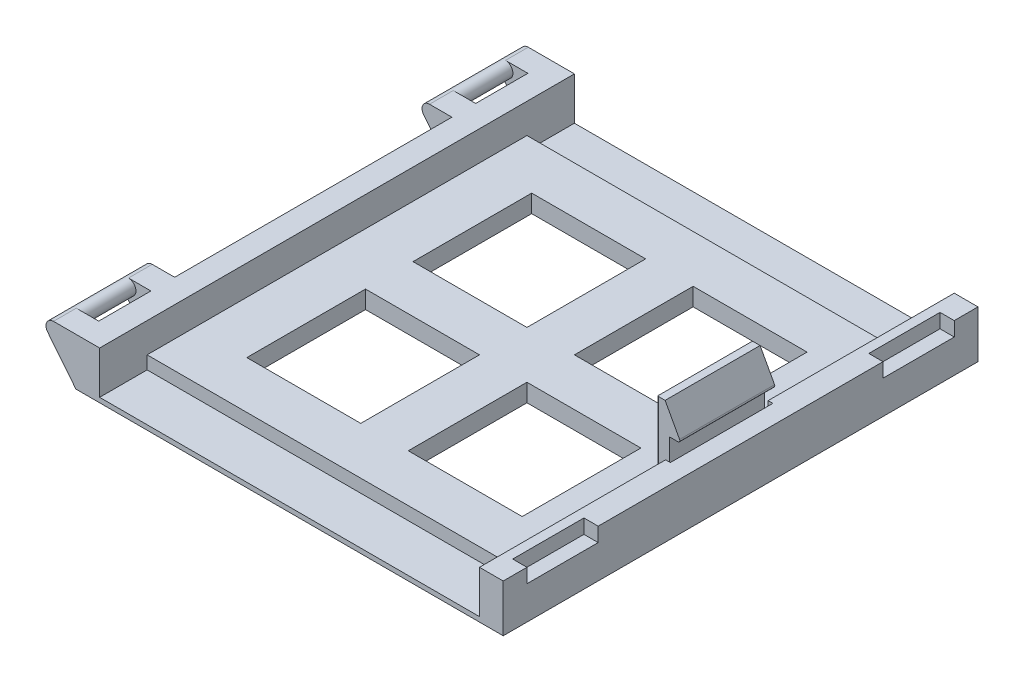
SolidWorks part; units mm, degrees
material "ABS"
ref_plane "Front Plane" through (0, 0, 0) normal (0, 0, 1) x (1, 0, 0)
ref_plane "Top Plane" through (0, 0, 0) normal (0, 1, 0) x (1, 0, 0)
ref_plane "Right Plane" through (0, 0, 0) normal (1, 0, 0) x (0, 0, -1)
sketch "Sketch1" plane through (0, 0, 0) normal (0, 0, 1) x (1, 0, 0)
  line L0 (23.8125, 6.35) -> (23.8125, 9.525)
  line L1 (-28.575, 3.175) -> (28.575, 3.175)
  line L2 (-28.575, 3.175) -> (-28.575, -3.175)
  line L3 (-28.575, -3.175) -> (28.575, -3.175)
  line L4 (28.575, 3.175) -> (28.575, -3.175)
  line L5 (-25.4, 3.175) -> (25.4, 3.175)
  line L6 (-25.4, 3.175) -> (-25.4, -0.7938)
  line L7 (-25.4, -0.7938) -> (25.4, -0.7938)
  line L8 (25.4, 3.175) -> (25.4, -0.7938)
  line L9 (-28.575, 3.175) -> (28.575, 3.175) construction
  line L10 (-28.575, 3.175) -> (-28.575, 9.525) construction
  line L11 (-28.575, 9.525) -> (28.575, 9.525) construction
  line L12 (28.575, 3.175) -> (28.575, 9.525) construction
  line L13 (-25.4, 3.175) -> (25.4, 3.175) construction
  line L14 (-25.4, 3.175) -> (-25.4, 7.1437) construction
  line L15 (-25.4, 7.1437) -> (25.4, 7.1437) construction
  line L16 (25.4, 3.175) -> (25.4, 7.1437) construction
  line L21 (25.4, -0.7938) -> (25.4, 5.588)
  line L22 (26.7661, 5.9634) -> (24.8285, 9.525)
  line L23 (24.8285, 9.525) -> (23.8125, 9.525)
  line L24 (-28.575, -3.175) -> (-32.3558, 1.5502)
  line L25 (-31.575, 3.175) -> (-28.575, 3.175)
  line L26 (-30.575, 2.175) -> (-28.575, 2.175) construction
  line L27 (25.4, -2.0638) -> (25.4, -0.7938)
  line L28 (23.8125, -0.7938) -> (23.8125, -2.0638)
  line L29 (23.1775, -2.0638) -> (23.1775, -0.7938)
  line L30 (23.8125, -0.7938) -> (23.8125, 6.35)
  line L33 (26.543, 5.588) -> (25.4, 5.588)
  line L34 (25.4, 5.588) -> (25.4, 3.175)
  line L35 (26.035, 3.175) -> (26.035, -2.0638)
  line L36 (26.797, 6.1869) -> (26.797, 5.0154) construction
  arc A0 (26.035, -2.0638) -> (25.4, -2.0638) centre (25.7175, -2.0638) cw
  arc A1 (23.8125, -2.0638) -> (23.1775, -2.0638) centre (23.495, -2.0638) cw
  arc A2 (-32.3558, 1.5502) -> (-31.575, 3.175) centre (-31.575, 2.175) cw
  circle A3 centre (-31.575, 2.175) radius 1
  arc A6 (26.7661, 5.9634) -> (26.543, 5.588) centre (26.543, 5.842) cw
  point P4 (0, -3.175)
  point P6 (-28.575, 0)
  point P16 (0, -0.7938)
  dimension "D10" = 1.27
  dimension "D13" = 1
  dimension "D21" = 0.254
  dimension "D6" = 0.3175
  dimension "D1" = 57.15
  dimension "D2" = 6.35
  dimension "D3" = 12.7
  dimension "D4" = 7.9375
  dimension "D5" = 50.8
  dimension "D7" = 1.016
  dimension "D8" = 1.5875
  dimension "D9" = 2.413
  dimension "D14" = 2
  dimension "D22" = 1.397
extrude "Boss-Extrude1" add sketch "Sketch1" along normal mid plane 63.5 contours L1 L8 L7 L6 L2 L3 | L28 L7 | L35 L1 L8 region at (-0.716, -1.5305, 0) region at (25.7175, 0.4305, 0) region at (23.495, -1.5551, 0)
extrude "Boss-Extrude2" add sketch "Sketch1<3>" along normal mid plane 12.7 contours L4 | A6 L30 L5 L34 L33 | L30 L7 L8 L5 | L0 region at (24.8321, 6.3195, 0) region at (24.6062, 1.1906, 0)
sketch "Sketch1<3>" plane through (0, 0, 0) normal (0, 0, 1) x (1, 0, 0) same geometry as "Sketch1"
extrude "Cut-Extrude2" cut sketch "Sketch1<6>" against normal mid plane 12.827 contours L35 L1 L8 region at (25.7175, 0.4305, 0)
sketch "Sketch1<6>" plane through (0, 0, 0) normal (0, 0, 1) x (1, 0, 0) same geometry as "Sketch1"
sketch "Sketch7" plane through (0, -0.7938, 0) normal (0, 1, 0) x (1, 0, 0)
  line L0 (26.035, 6.35) -> (23.9395, 6.35)
  line L3 (23.9395, -6.35) -> (26.035, -6.35)
  line L6 (23.8125, 6.223) -> (23.8125, -6.223)
  line L7 (23.8125, 6.35) -> (25.4, 6.35) construction
  line L10 (26.7661, -6.35) -> (24.8285, -6.35) construction
  line L11 (26.035, 6.4135) -> (26.035, -6.4135) construction
  line L12 (26.7661, 6.35) -> (24.8285, 6.35) construction
  line L13 (23.8125, -6.35) -> (23.8125, 6.35) construction
  arc A0 (23.9395, 6.35) -> (23.8125, 6.223) centre (23.9395, 6.223) ccw
  arc A1 (23.8125, -6.223) -> (23.9395, -6.35) centre (23.9395, -6.223) ccw
  dimension "D1" = 0.127
sketch "Sketch8" plane through (26.035, 0, 0) normal (1, 0, 0) x (0, 0, -1)
  line L4 (-6.858, -2.6988) -> (-6.858, 9.525)
  line L5 (-6.858, 9.525) -> (-6.35, 9.525)
  line L6 (-6.35, 9.525) -> (-6.35, -2.6988)
  arc A0 (-6.35, -2.6988) -> (-6.858, -2.6988) centre (-6.604, -2.6988) cw
  dimension "D1" = 0.254
  dimension "D2" = 1.905
sweep "Cut-Sweep1" cut profiles "Sketch8" path "Sketch7"
extrude "Boss-Extrude3" add sketch "Sketch1<7>" against normal blind 3.048 from surface contours A2 L24 L2 L25 | A2 A3 region at (-29.726, 0.631, 0) region at (-31.575, 2.175, 0) starting at face at (0, 0.5953, 31.75)
sketch "Sketch1<7>" plane through (0, 0, 0) normal (0, 0, 1) x (1, 0, 0) same geometry as "Sketch1"
extrude "Boss-Extrude5" add sketch "Sketch1<9>" along normal blind 3.048 from surface contours A2 L24 L2 L25 | A2 A3 region at (-29.726, 0.631, 0) region at (-31.575, 2.175, 0) starting at face at (0, 0.5953, -31.75)
sketch "Sketch1<9>" plane through (0, 0, 0) normal (0, 0, 1) x (1, 0, 0) same geometry as "Sketch1"
ref_plane "Plane1" through (0, 0, 21.717) normal (0, 0, 1) x (1, 0, 0)
ref_plane "Plane2" through (0, 0, -21.717) normal (0, 0, -1) x (-1, 0, 0)
extrude "Boss-Extrude7" add sketch "Sketch1<13>" against normal blind 3.175 from surface contours A3 L24 L2 L25 | A2 A3 region at (-29.726, 0.631, 0) region at (-31.575, 2.175, 0) starting at plane "Plane1"
sketch "Sketch1<13>" plane through (0, 0, 0) normal (0, 0, 1) x (1, 0, 0) same geometry as "Sketch1"
extrude "Boss-Extrude8" add sketch "Sketch1<14>" along normal blind 3.175 from surface contours A3 L24 L2 L25 | A2 A3 region at (-29.726, 0.631, 0) region at (-31.575, 2.175, 0) starting at plane "Plane2"
sketch "Sketch1<14>" plane through (0, 0, 0) normal (0, 0, 1) x (1, 0, 0) same geometry as "Sketch1"
extrude "Boss-Extrude6" add sketch "Sketch1<10>" against normal up to surface (-18.542 mm away) from surface contours A2 A3 region at (-31.575, 2.175, 0) up to face at (-30.3979, 1.2427, 18.542) starting at face at (-3.9852, 0.7287, 31.75)
sketch "Sketch1<10>" plane through (0, 0, 0) normal (0, 0, 1) x (1, 0, 0) same geometry as "Sketch1"
extrude "Boss-Extrude9" add sketch "Sketch1<16>" along normal up to surface (-18.542 mm away) from surface contours A2 A3 region at (-31.575, 2.175, 0) up to face at (-30.3979, 1.2427, -18.542) starting at face at (-3.9852, 0.7287, -31.75)
sketch "Sketch1<16>" plane through (0, 0, 0) normal (0, 0, 1) x (1, 0, 0) same geometry as "Sketch1"
sketch "Sketch2" plane through (0, 3.175, 0) normal (0, 1, 0) x (1, 0, 0)
  line L1 (-32.575, 50.8) -> (30.1625, 50.8)
  line L2 (-32.575, 50.8) -> (-32.575, 6.35)
  line L3 (-32.575, 6.35) -> (30.1625, 6.35)
  line L4 (30.1625, 50.8) -> (30.1625, 6.35)
  line L5 (-32.575, -50.8) -> (30.1625, -50.8)
  line L6 (-32.575, -50.8) -> (-32.575, -6.35)
  line L7 (-32.575, -6.35) -> (30.1625, -6.35)
  line L8 (30.1625, -50.8) -> (30.1625, -6.35)
extrude "Cut-Extrude3" [suppressed] cut sketch "Sketch2" against normal through all
sketch "Sketch3" plane through (0, -0.7938, 0) normal (0, 1, 0) x (1, 0, 0)
  line L0 (-3.175, 33.3375) -> (3.175, 33.3375) construction
  line L1 (-18.415, 41.275) -> (-3.175, 41.275)
  line L2 (-18.415, 41.275) -> (-18.415, 25.4)
  line L3 (-18.415, 25.4) -> (-3.175, 25.4)
  line L4 (-3.175, 41.275) -> (-3.175, 25.4)
  line L5 (3.175, 41.275) -> (18.415, 41.275)
  line L6 (3.175, 41.275) -> (3.175, 25.4)
  line L7 (3.175, 25.4) -> (18.415, 25.4)
  line L8 (18.415, 41.275) -> (18.415, 25.4)
  line L9 (-18.415, 19.05) -> (-3.175, 19.05)
  line L10 (-18.415, 19.05) -> (-18.415, 3.175)
  line L11 (-18.415, 3.175) -> (-3.175, 3.175)
  line L12 (-3.175, 19.05) -> (-3.175, 3.175)
  line L13 (3.175, 19.05) -> (18.415, 19.05)
  line L14 (3.175, 19.05) -> (3.175, 3.175)
  line L15 (3.175, 3.175) -> (18.415, 3.175)
  line L16 (18.415, 19.05) -> (18.415, 3.175)
  line L17 (-18.415, -3.175) -> (-3.175, -3.175)
  line L18 (-18.415, -3.175) -> (-18.415, -19.05)
  line L19 (-18.415, -19.05) -> (-3.175, -19.05)
  line L20 (-3.175, -3.175) -> (-3.175, -19.05)
  line L21 (3.175, -3.175) -> (18.415, -3.175)
  line L22 (3.175, -3.175) -> (3.175, -19.05)
  line L23 (3.175, -19.05) -> (18.415, -19.05)
  line L24 (18.415, -3.175) -> (18.415, -19.05)
  line L25 (-18.415, -25.4) -> (-3.175, -25.4)
  line L26 (-18.415, -25.4) -> (-18.415, -41.275)
  line L27 (-18.415, -41.275) -> (-3.175, -41.275)
  line L28 (-3.175, -25.4) -> (-3.175, -41.275)
  line L29 (3.175, -25.4) -> (18.415, -25.4)
  line L30 (3.175, -25.4) -> (3.175, -41.275)
  line L31 (3.175, -41.275) -> (18.415, -41.275)
  line L32 (18.415, -25.4) -> (18.415, -41.275)
  line L33 (-10.795, 3.175) -> (-10.795, -3.175) construction
  line L34 (-10.795, 25.4) -> (-10.795, 19.05) construction
  line L35 (-10.795, -19.05) -> (-10.795, -25.4) construction
  line L36 (-25.4, -31.75) -> (-25.4, 31.75) construction
  line L37 (-25.4, 31.75) -> (25.4, 31.75) construction
  line L38 (3.4925, 21.717) -> (-3.4925, 21.717) construction
  line L39 (-28.575, 28.702) -> (-27.305, 28.702)
  line L40 (-28.575, 28.702) -> (-28.575, 21.717)
  line L41 (-28.575, 21.717) -> (-27.305, 21.717)
  line L42 (-27.305, 28.702) -> (-27.305, 21.717)
  line L43 (-3.4925, -21.717) -> (3.4925, -21.717) construction
  line L44 (-28.575, -28.702) -> (-27.305, -28.702)
  line L45 (-28.575, -28.702) -> (-28.575, -21.717)
  line L46 (-28.575, -21.717) -> (-27.305, -21.717)
  line L47 (-27.305, -28.702) -> (-27.305, -21.717)
  point P36 (-10.795, 0)
  point P38 (0, 33.3375)
  dimension "D1" = 6.985
  dimension "D2" = 9.525
  dimension "D3" = 6.35
  dimension "D4" = 6.35
  dimension "D5" = 1.27
extrude "Cut-Extrude4" cut sketch "Sketch3" against normal through all both and the other way through all contours L16 L13 L14 L15 | L12 L9 L10 L11 | L24 L21 L22 L23 | L20 L17 L18 L19 region at (-10.795, -0.7938, -11.1125) region at (10.795, -0.7938, -11.1125) region at (-10.795, -0.7938, 11.1125) region at (10.795, -0.7938, 11.1125)
sketch "Sketch4" plane through (0, -3.175, 0) normal (0, -1, 0) x (1, 0, 0)
  line L0 (28.575, 31.75) -> (28.575, -31.75) construction
  line L1 (-25.4, 31.75) -> (28.575, 31.75)
  line L2 (-25.4, 31.75) -> (-25.4, 8.35)
  line L3 (-25.4, 8.35) -> (28.575, 8.35)
  line L4 (28.575, 31.75) -> (28.575, 8.35)
  line L5 (-25.4, 31.75) -> (-25.4, -31.75) construction
  line L6 (28.575, -31.75) -> (-25.4, -31.75)
  line L7 (28.575, -31.75) -> (28.575, -8.35)
  line L8 (28.575, -8.35) -> (-25.4, -8.35)
  line L9 (-25.4, -31.75) -> (-25.4, -8.35)
  line L10 (23.8125, 6.35) -> (25.4, 6.35) construction
  dimension "D1" = 2
extrude "Cut-Extrude5" [suppressed] cut sketch "Sketch4" against normal through all
sketch "Sketch5" plane through (0, 0, 31.75) normal (0, 0, 1) x (1, 0, 0)
  line L0 (-3.5976, 3.81) -> (3.5976, 3.81) construction
  line L1 (-25.4, -0.7938) -> (25.4, -0.7938)
  line L2 (-25.4, -0.7938) -> (-25.4, -2.54)
  line L3 (-25.4, -2.54) -> (25.4, -2.54)
  line L4 (25.4, -0.7938) -> (25.4, -2.54)
  line L6 (25.4, 3.175) -> (25.4, 7.1437) construction
  line L7 (-25.4, 7.1437) -> (25.4, 7.1437) construction
  line L8 (-25.4, 7.1437) -> (-25.4, 8.89) construction
  line L9 (-25.4, 8.89) -> (25.4, 8.89) construction
  line L10 (25.4, 7.1437) -> (25.4, 8.89) construction
  point P15 (0, 3.81)
  point P16 (0, 8.89)
  dimension "D1" = 5.08
  dimension "D2" = 6.35
extrude "Cut-Extrude6" cut sketch "Sketch5" against normal blind 6.35
mirror "Mirror1" about plane through (0, 0, 0) normal (0, 0, 1) of "Cut-Extrude6"
sketch "Sketch6" plane through (28.575, 0, 0) normal (1, 0, 0) x (0, 0, -1)
  line L0 (-31.75, 3.175) -> (31.75, 3.175) construction
  line L1 (-28.575, 3.175) -> (-19.05, 3.175)
  line L2 (-28.575, 3.175) -> (-28.575, 1.27)
  line L3 (-28.575, 1.27) -> (-19.05, 1.27)
  line L4 (-19.05, 3.175) -> (-19.05, 1.27)
  line L5 (-31.75, 3.175) -> (-31.75, -3.175) construction
  line L6 (-19.05, 2.2225) -> (19.05, 2.2225) construction
  line L7 (19.05, 3.175) -> (28.575, 3.175)
  line L8 (19.05, 3.175) -> (19.05, 1.27)
  line L9 (19.05, 1.27) -> (28.575, 1.27)
  line L10 (28.575, 3.175) -> (28.575, 1.27)
  point P16 (0, 2.2225)
  dimension "D1" = 9.525
  dimension "D2" = 1.905
  dimension "D3" = 3.175
extrude "Cut-Extrude7" cut sketch "Sketch6" against normal blind 1.905
